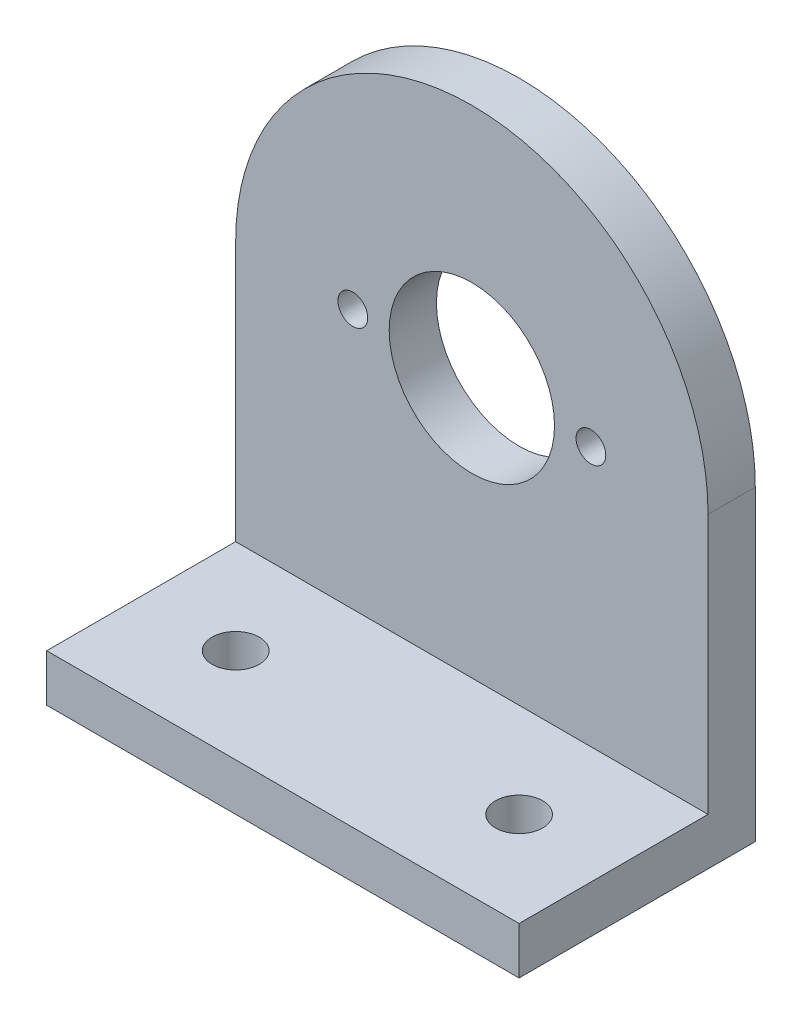
SolidWorks part; units mm, degrees
ref_plane "Front Plane" through (0, 0, 0) normal (0, 0, 1) x (1, 0, 0)
ref_plane "Top Plane" through (0, 0, 0) normal (0, 1, 0) x (1, 0, 0)
ref_plane "Right Plane" through (0, 0, 0) normal (1, 0, 0) x (0, 0, -1)
sketch "Sketch1" plane through (0, 0, 0) normal (0, 0, 1) x (1, 0, 0)
  line L1 (-15.875, 0) -> (15.875, 0)
  line L2 (-15.875, 0) -> (-15.875, -20.6375)
  line L3 (-15.875, -20.6375) -> (15.875, -20.6375)
  line L4 (15.875, 0) -> (15.875, -20.6375)
  circle A0 centre (0, 0) radius 15.875
  arc A2 (-15.875, 0) -> (15.875, 0) centre (0, 0) ccw
  point P6 (15.875, 0)
  point P7 (15.875, -20.6375)
  dimension "D1" = 31.75
  dimension "D2" = 20.6375
extrude "Boss-Extrude1" add sketch "Sketch1" along normal blind 3.175 contours A0 | L2 L1 L4 L3
sketch "Sketch3" plane through (0, 0, 3.175) normal (0, 0, 1) x (1, 0, 0)
  circle A0 centre (0, 0) radius 5.5562
  dimension "D1" = 11.1125
extrude "Cut-Extrude1" cut sketch "Sketch3" against normal through all
sketch "Sketch4" plane through (0, 0, 3.175) normal (0, 0, 1) x (1, 0, 0)
  line L0 (15.875, 0) -> (15.875, -20.6375) construction
  line L1 (-15.875, -20.6375) -> (15.875, -20.6375)
  line L2 (-15.875, -20.6375) -> (-15.875, -17.4625)
  line L3 (-15.875, -17.4625) -> (15.875, -17.4625)
  line L4 (15.875, -20.6375) -> (15.875, -17.4625)
  dimension "D1" = 3.175
extrude "Boss-Extrude2" add sketch "Sketch4" along normal blind 12.7
sketch "Sketch5" plane through (0, -17.4625, 0) normal (0, 1, 0) x (1, 0, 0)
  line L0 (-15.875, -9.525) -> (15.875, -9.525) construction
  line L1 (-15.875, -15.875) -> (-15.875, -3.175) construction
  line L2 (15.875, -15.875) -> (15.875, -3.175) construction
  line L3 (0, -3.175) -> (0, -15.875) construction
  line L4 (15.875, -3.175) -> (-15.875, -3.175) construction
  line L5 (15.875, -15.875) -> (-15.875, -15.875) construction
  circle A0 centre (-9.525, -9.525) radius 1.5875
  circle A1 centre (9.525, -9.525) radius 1.5875
  point P14 (-7.2474, -9.525)
  dimension "D1" = 3.175
  dimension "D2" = 9.525
extrude "Cut-Extrude2" cut sketch "Sketch5" against normal through all
hole_wizard "Ø2.0mm Dowel Hole1" positions "Sketch8" profile "Sketch9" hole size "Ø2.0" standard "ANSI Metric"
sketch "Sketch8" plane through (0, 0, 3.175) normal (0, 0, 1) x (1, 0, 0)
  line L0 (-15.875, 0) -> (15.875, 0) construction
  point P0 (-8.001, 0)
  point P2 (8.001, 0)
  point P11 (11.6847, 0)
  point P12 (-10.4143, 0)
  dimension "D1" = 16.002
  dimension "D2" = 8.001
sketch "Sketch9" plane through (-8.001, 0, 3.175) normal (1, 0, 0) x (0, -1, 0)
  line L0 (0, 0) -> (0, 13.3009)
  line L1 (0, 13.3009) -> (1, 12.7)
  line L2 (1, 12.7) -> (1, 0)
  line L5 (1, 0) -> (0, 0)
  line L10 (0, 13.3009) -> (-1, 12.7) construction
  line L11 (0, -6.35) -> (0, 107.95) construction
  dimension "Hole Dia." = 2
  dimension "Hole Depth" = 12.7
  dimension "Drill Angle" = 118
